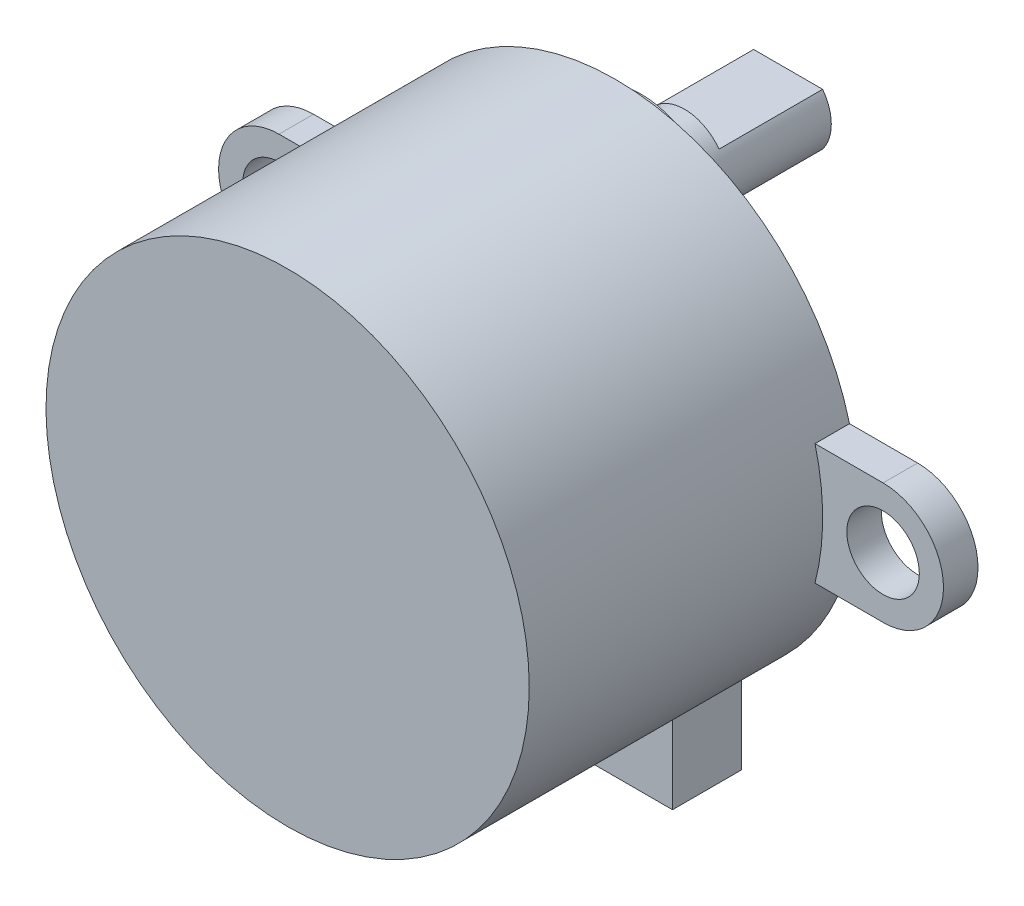
SolidWorks part; units mm, degrees
ref_plane "Front Plane" through (0, 0, 0) normal (0, 0, 1) x (1, 0, 0)
ref_plane "Top Plane" through (0, 0, 0) normal (0, 1, 0) x (1, 0, 0)
ref_plane "Right Plane" through (0, 0, 0) normal (1, 0, 0) x (0, 0, -1)
sketch "Sketch2" plane through (0, 0, 0) normal (0, 0, 1) x (1, 0, 0)
  line L0 (-17.5, 0) -> (17.5, 0) construction
  line L1 (17.5, 3.5) -> (13.5554, 3.5)
  line L2 (17.5, -3.5) -> (13.5554, -3.5)
  line L3 (7.3, -11.9461) -> (7.3, -17)
  line L4 (7.3, -17) -> (-7.3, -17)
  line L5 (-7.3, -17) -> (-7.3, -11.9461)
  circle A0 centre (0, 0) radius 14
  arc A2 (17.5, -3.5) -> (17.5, 3.5) centre (17.5, 0) ccw
  circle A3 centre (17.5, 0) radius 2.1
  point P2 (0, 0)
  point P15 (-11.481, -19.3741)
  point P16 (0, -17)
  dimension "D2" = 28
  dimension "D3" = 3.5
  dimension "D4" = 4.2
  dimension "D1" = 35
  dimension "D5" = 17
  dimension "D6" = 14.6
extrude "Boss-Extrude1" add sketch "Sketch2" along normal blind 19 contours A0 L0 | L0 A0 region at (0, 5.9418, 0) region at (0, -5.9418, 0)
extrude "Boss-Extrude2" add sketch "Sketch2<3>" along normal blind 2 contours L2 A2 L1 A0 A3 region at (20.8978, 0, 0)
sketch "Sketch2<3>" plane through (0, 0, 0) normal (0, 0, 1) x (1, 0, 0) same geometry as "Sketch2"
mirror "Mirror1" about plane through (0, 0, 0) normal (1, 0, 0) of "Boss-Extrude2"
sketch "Sketch3" plane through (0, 0, 0) normal (0, 0, 1) x (1, 0, 0)
  circle A0 centre (0, 8) radius 4.5
  point P2 (0, 0)
  dimension "D1" = 9
  dimension "D2" = 8
extrude "Boss-Extrude3" add sketch "Sketch2<4>" along normal blind 4 contours A0 L5 L4 L3 region at (0, -15.1184, 0)
sketch "Sketch2<4>" plane through (0, 0, 0) normal (0, 0, 1) x (1, 0, 0) same geometry as "Sketch2"
extrude "Boss-Extrude4" add sketch "Sketch3" against normal blind 1.5 contours A0
sketch "Sketch5" plane through (0, 0, 0) normal (0, 0, 1) x (1, 0, 0)
  line L0 (2, 9.5) -> (-2, 9.5)
  line L1 (-2, 6.5) -> (2, 6.5)
  line L2 (0, 9.5) -> (0, 6.5) construction
  circle A0 centre (0, 8) radius 2.5
  point P9 (0, 8)
  dimension "D1" = 5
  dimension "D2" = 3
extrude "Boss-Extrude5" add sketch "Sketch5" against normal blind 10 contours A0
sketch "Sketch7" plane through (0, 0, -10) normal (0, 0, -1) x (-1, 0, 0)
  line L0 (2, 6.5) -> (-2, 6.5) construction
  line L1 (-2, 9.5) -> (2, 9.5) construction
  line L2 (2, 6.5) -> (-2, 6.5)
  line L3 (-2, 9.5) -> (2, 9.5)
  circle A0 centre (0, 8) radius 2.5 construction
  circle A1 centre (0, 8) radius 2.5
  circle M1 centre (0, 8) radius 2.5
extrude "Cut-Extrude1" cut sketch "Sketch7" against normal blind 6 contours L3 M1 | L2 M1 region at (0, 6.0922, -10) region at (0, 9.9078, -10)
